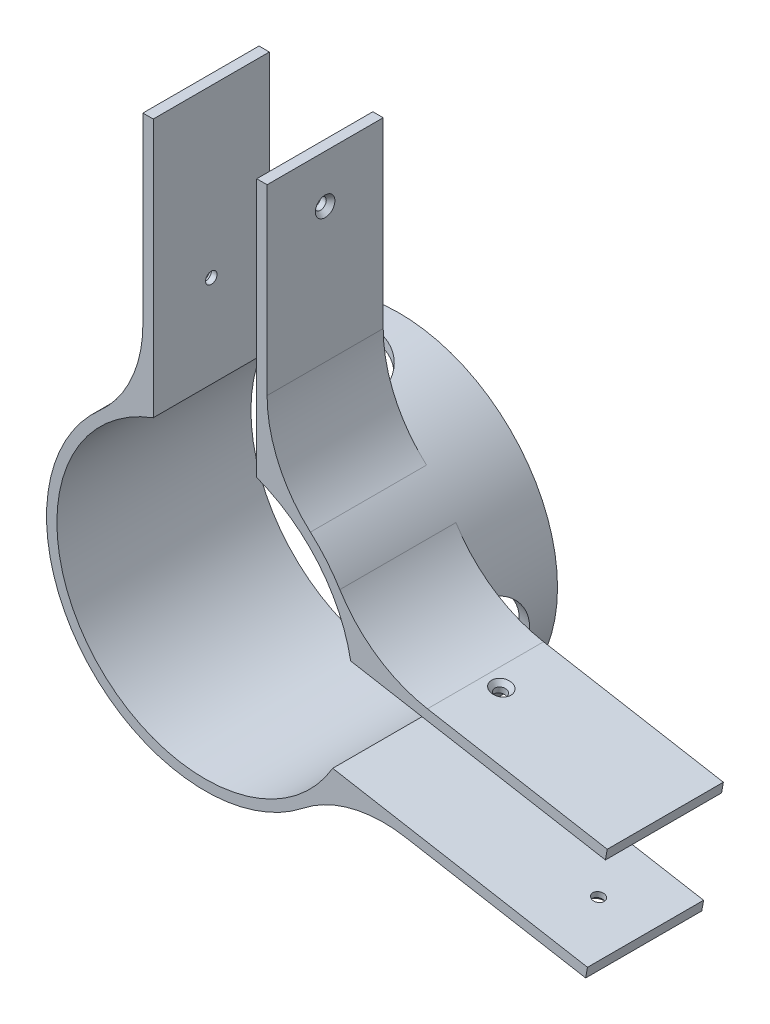
SolidWorks part; units mm, degrees
ref_plane "Plan de face" through (0, 0, 0) normal (0, 0, 1) x (1, 0, 0)
ref_plane "Plan de dessus" through (0, 0, 0) normal (0, 1, 0) x (1, 0, 0)
ref_plane "Plan de droite" through (0, 0, 0) normal (1, 0, 0) x (0, 0, -1)
sketch "Esquisse1" plane through (0, 0, 0) normal (0, 0, 1) x (1, 0, 0)
  line L0 (0, 0) -> (0, 24.5) construction
  line L1 (0, 0) -> (22.5521, -3.9765) construction
  circle A0 centre (0, 0) radius 22.9
  circle A1 centre (0, 0) radius 24.5
  dimension "D1" = 45.8
  dimension "D3" = 100
  dimension "D2" = 1.6
extrude "Boss.-Extru.1" add sketch "Esquisse1" along normal blind 30
sketch "Esquisse2" plane through (0, 0, 0) normal (0, 1, 0) x (1, 0, 0)
  line L1 (-24.5, -30) -> (24.5, -30) construction
  line L2 (-8, -30) -> (-8, -12.0501)
  line L3 (8, -12.0501) -> (8, -30)
  line L6 (-8, -30) -> (8, -30)
  arc A0 (-8, -12.0501) -> (8, -12.0501) centre (0, -12.0501) cw
  dimension "D1" = 16
extrude "Enlèv. mat.-Extru.1" cut sketch "Esquisse2" along normal through all
sketch "Esquisse3" plane through (-8, 0, 0) normal (1, 0, 0) x (0, 0, -1)
  line L0 (-12.0501, 21.4572) -> (-30, 21.4572)
  line L1 (-12.0501, 21.4572) -> (-12.0501, 61.4572)
  line L2 (-30, 21.4572) -> (-30, 61.4572)
  line L3 (-12.0501, 61.4572) -> (-30, 61.4572)
  dimension "D1" = 40
extrude "Boss.-Extru.2" add sketch "Esquisse3" against normal blind 1.6
sketch "Esquisse4" plane through (8, 0, 0) normal (-1, 0, 0) x (0, 0, 1)
  line L0 (30, 21.4572) -> (12.0501, 21.4572)
  line L1 (30, 21.4572) -> (30, 61.4572)
  line L2 (12.0501, 21.4572) -> (12.0501, 61.4572)
  line L3 (30, 61.4572) -> (12.0501, 61.4572)
  dimension "D1" = 40
extrude "Boss.-Extru.3" add sketch "Esquisse4" against normal blind 1.6
fillet "Congé1" radius 20 2 edges at (-9.6, 22.5409, 21.0251) (9.6, 22.5409, 21.0251)
hole_wizard "Fraisage pour vis à tête fraisée bombée #01" positions "Esquisse5" profile "Esquisse6" countersink size "#0" standard "Ansi Inch" end condition up to next
sketch "Esquisse5" plane through (9.6, 0, 0) normal (1, 0, 0) x (0, 0, -1)
  point P0 (-21.0251, 54.083)
  point P1 (-21.0251, 54.083)
sketch "Esquisse6" plane through (9.6, 54.083, 21.0251) normal (0, 1, 0) x (0, 0, -1)
  line L0 (0, 0) -> (0, 1.6)
  line L1 (0, 1.6) -> (0.889, 1.6)
  line L2 (0.889, 1.6) -> (0.889, 0.7159)
  line L3 (0.889, 0.7159) -> (1.5113, 0)
  line L5 (1.5113, 0) -> (0, 0)
  line L6 (-0.889, 0.7159) -> (-1.5113, 0) construction
  line L11 (0, -6.35) -> (0, 107.95) construction
  dimension "Diamètre du perçage jusqu'au prochain" = 1.778
  dimension "Profondeur du perçage jusqu'au prochain" = 1.6
  dimension "Diamètre du fraisage entrant" = 3.0226
  dimension "Angle du fraisage entrant" = 82
hole_wizard "Fraisage pour vis à tête fraisée bombée #02" positions "Esquisse7" profile "Esquisse8" countersink size "#0" standard "Ansi Inch" end condition up to next
sketch "Esquisse7" plane through (-9.6, 0, 0) normal (-1, 0, 0) x (0, 0, 1)
  point P0 (21.0251, 35.7147)
  point P1 (21.0251, 35.7147)
sketch "Esquisse8" plane through (-9.6, 35.7147, 21.0251) normal (0, 1, 0) x (0, 0, 1)
  line L0 (0, 0) -> (0, 1.6)
  line L1 (0, 1.6) -> (0.889, 1.6)
  line L2 (0.889, 1.6) -> (0.889, 0.7159)
  line L3 (0.889, 0.7159) -> (1.5113, 0)
  line L5 (1.5113, 0) -> (0, 0)
  line L6 (-0.889, 0.7159) -> (-1.5113, 0) construction
  line L11 (0, -6.35) -> (0, 107.95) construction
  dimension "Diamètre du perçage jusqu'au prochain" = 1.778
  dimension "Profondeur du perçage jusqu'au prochain" = 1.6
  dimension "Diamètre du fraisage entrant" = 3.0226
  dimension "Angle du fraisage entrant" = 82
pattern_circular "Répétition circulaire1" count 2 over 100 about axis through (0, 0, 0) along (0, 0, 1) of "Enlèv. mat.-Extru.1", "Boss.-Extru.2", "Boss.-Extru.3", "Fraisage pour vis à tête fraisée bombée #01", "Fraisage pour vis à tête fraisée bombée #02", "Congé1" reverse direction yes
